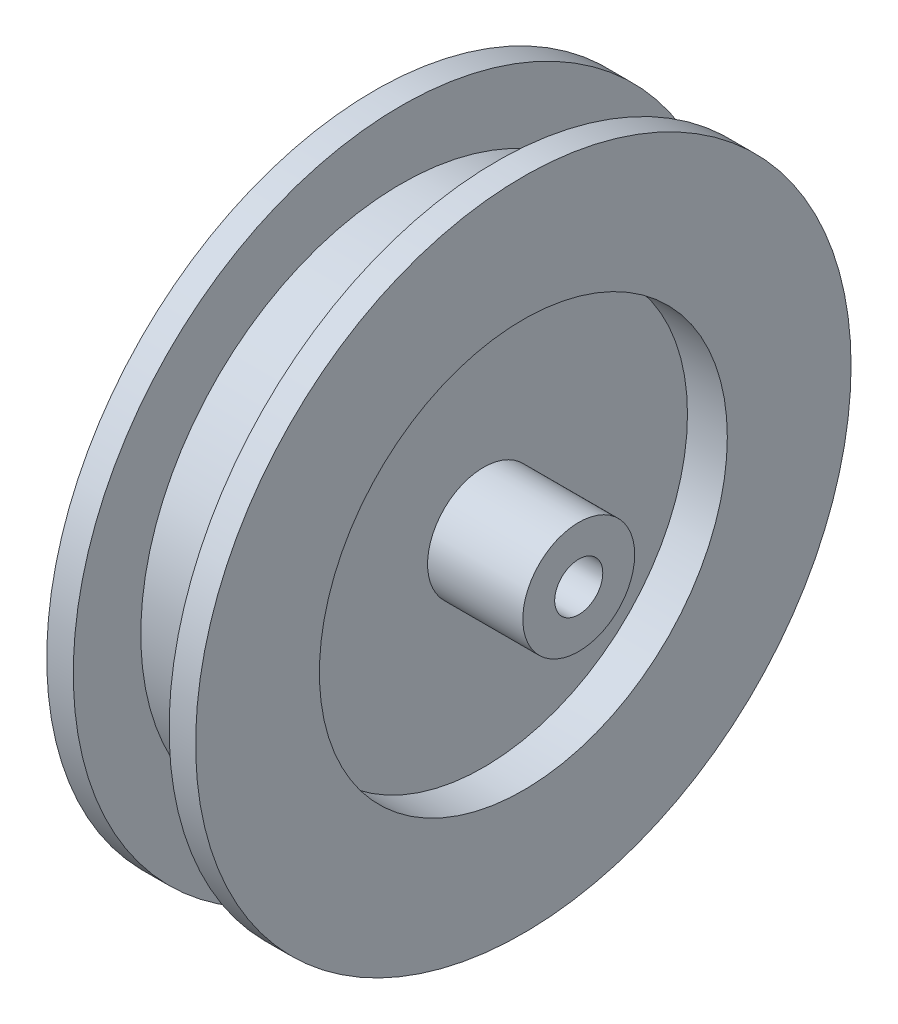
SolidWorks part; units mm, degrees
ref_plane "Front Plane" through (0, 0, 0) normal (0, 0, 1) x (1, 0, 0)
ref_plane "Top Plane" through (0, 0, 0) normal (0, 1, 0) x (1, 0, 0)
ref_plane "Right Plane" through (0, 0, 0) normal (1, 0, 0) x (0, 0, -1)
sketch "Sketch1" plane through (0, 0, 0) normal (1, 0, 0) x (0, 0, -1)
  circle A0 centre (0, 0) radius 76.2635
  dimension "D1" = 152.527
extrude "Boss-Extrude1" add sketch "Sketch1" along normal mid plane 34.6456
sketch "Sketch2" plane through (17.3228, 0, 0) normal (1, 0, 0) x (0, 0, -1)
  circle A0 centre (0, 0) radius 47.4663
  dimension "D1" = 94.9325
extrude "Cut-Extrude1" cut sketch "Sketch2" against normal blind 9.271
extrude "Cut-Extrude2" cut sketch "Sketch2<2>" along normal blind 18.796 from surface starting at face at (-17.3228, 0, -76.2635)
sketch "Sketch2<2>" plane through (17.3228, 0, 0) normal (1, 0, 0) x (0, 0, -1) same geometry as "Sketch2"
sketch "Sketch3" plane through (17.3228, 0, 0) normal (1, 0, 0) x (0, 0, -1)
  circle A0 centre (0, 0) radius 60.5536
  dimension "D1" = 121.1072
extrude "Cut-Extrude3" cut sketch "Sketch3" against normal offset from surface (22.3012 mm away) 6.1722 from offset 6.1722 flip side to cut up to face at (-17.3228, 0, -76.2635) offset against normal yes
sketch "Sketch4" plane through (8.0518, 0, 0) normal (1, 0, 0) x (0, 0, -1)
  circle A0 centre (0, 0) radius 13.0175
  dimension "D1" = 26.035
extrude "Boss-Extrude2" add sketch "Sketch4" along normal blind 22.1615
sketch "Sketch5" plane through (30.2133, 0, 0) normal (1, 0, 0) x (0, 0, -1)
  circle A0 centre (0, 0) radius 5.5943
  dimension "D1" = 11.1887
extrude "Cut-Extrude4" cut sketch "Sketch5" against normal through all
